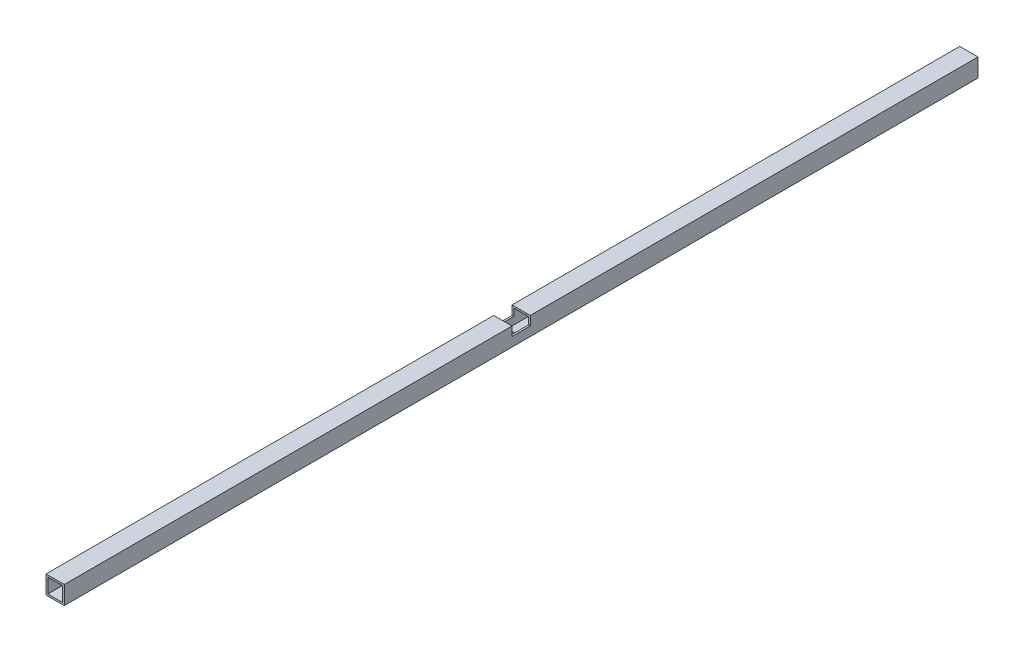
SolidWorks part; units mm, degrees
ref_plane "Plan de face" through (0, 0, 0) normal (0, 0, 1) x (1, 0, 0)
ref_plane "Plan de dessus" through (0, 0, 0) normal (0, 1, 0) x (1, 0, 0)
ref_plane "Plan de droite" through (0, 0, 0) normal (1, 0, 0) x (0, 0, -1)
sketch "Esquisse3" plane through (0, 0, 0) normal (0, 0, 1) x (1, 0, 0)
  line L1 (-44.7155, 17.9023) -> (-34.7155, 17.9023)
  line L2 (-44.7155, 17.9023) -> (-44.7155, 7.9023)
  line L3 (-44.7155, 7.9023) -> (-34.7155, 7.9023)
  line L4 (-34.7155, 17.9023) -> (-34.7155, 7.9023)
extrude "Boss.-Extru.3" add sketch "Esquisse3" along normal blind 500 and the other way blind 0.0001
sketch "Esquisse4" plane through (0, 17.9023, 0) normal (0, 1, 0) x (-1, 0, 0)
  line L0 (44.7155, 500) -> (44.7155, -0.0001) construction
  line L1 (44.7155, 245) -> (34.7155, 245)
  line L2 (44.7155, 245) -> (44.7155, 255)
  line L3 (44.7155, 255) -> (34.7155, 255)
  line L4 (34.7155, 245) -> (34.7155, 255)
  line L5 (34.7155, 500) -> (34.7155, -0.0001) construction
  dimension "D1" = 10
  dimension "D2" = 245
extrude "Enlèv. mat.-Extru.1" cut sketch "Esquisse4" against normal blind 5
sketch "Esquisse8" plane through (0, 0, 500) normal (0, 0, 1) x (1, 0, 0)
  line L0 (-34.7155, 7.9023) -> (-34.7155, 17.9023) construction
  line L1 (-43.7155, 16.9222) -> (-35.7155, 16.9222)
  line L2 (-43.7155, 16.9222) -> (-43.7155, 8.9023)
  line L3 (-43.7155, 8.9023) -> (-35.7155, 8.9023)
  line L4 (-35.7155, 16.9222) -> (-35.7155, 8.9023)
  line L5 (-44.7155, 7.9023) -> (-34.7155, 7.9023) construction
  dimension "D1" = 1
  dimension "D2" = 1
extrude "Enlèv. mat.-Extru.4" cut sketch "Esquisse8" against normal through all
hole_wizard "Trou pour taraudage pour trou taraudé M4x0.72" positions "Esquisse16" profile "Esquisse15" hole size "M4x0.7" standard "Ansi Métrique"
sketch "Esquisse16" plane through (0, 8.9023, 0) normal (0, 1, 0) x (-1, 0, 0)
  line L0 (34.7155, 500) -> (44.7155, 500) construction
  line L1 (44.7155, 245) -> (44.7155, 255) construction
  point P0 (39.7155, 250)
  dimension "D1" = 250
  dimension "D2" = 5
sketch "Esquisse15" plane through (-39.7155, 8.9023, 250) normal (1, 0, 0) x (0, 0, 1)
  line L0 (0, 0) -> (0, 10.9914)
  line L1 (0, 10.9914) -> (1.65, 10)
  line L2 (1.65, 10) -> (1.65, 0)
  line L5 (1.65, 0) -> (0, 0)
  line L10 (0, 10.9914) -> (-1.65, 10) construction
  line L11 (0, -6.35) -> (0, 107.95) construction
  dimension "Diamètre du perçage" = 3.3
  dimension "Profondeur du perçage" = 10
  dimension "Angle de pointe" = 118
